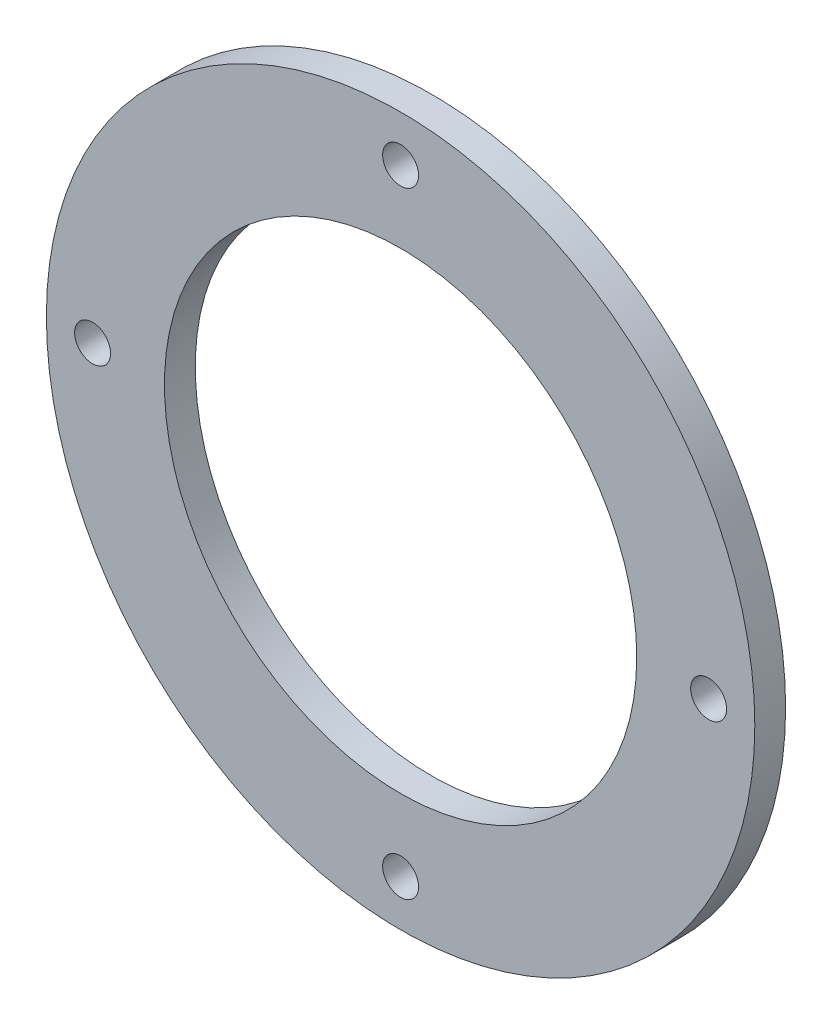
SolidWorks part; units mm, degrees
ref_plane "Front Plane" through (0, 0, 0) normal (0, 0, 1) x (1, 0, 0)
ref_plane "Top Plane" through (0, 0, 0) normal (0, 1, 0) x (1, 0, 0)
ref_plane "Right Plane" through (0, 0, 0) normal (1, 0, 0) x (0, 0, -1)
sketch "Sketch1" plane through (0, 0, 0) normal (0, 0, 1) x (1, 0, 0)
  circle A0 centre (0, 0) radius 23
  circle A1 centre (0, 0) radius 34.5
  circle A2 centre (0, 30) radius 1.75
  circle A3 centre (30, 0) radius 1.75
  circle A4 centre (0, -30) radius 1.75
  circle A5 centre (-30, 0) radius 1.75
  circle A6 centre (0, 0) radius 30 construction
  point P15 (0, 0)
  dimension "D1" = 69
  dimension "D2" = 46
  dimension "D3" = 3.5
  dimension "D5" = 60
  dimension "D4" = 4
extrude "Boss-Extrude1" add sketch "Sketch1" along normal blind 3
